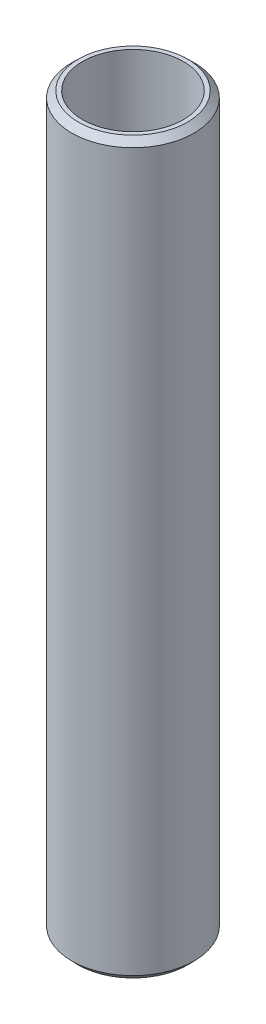
SolidWorks part; units mm, degrees
ref_plane "Front Plane" through (0, 0, 0) normal (0, 0, 1) x (1, 0, 0)
ref_plane "Top Plane" through (0, 0, 0) normal (0, 1, 0) x (1, 0, 0)
ref_plane "Right Plane" through (0, 0, 0) normal (1, 0, 0) x (0, 0, -1)
sketch "Sketch1" plane through (0, 0, 0) normal (0, 1, 0) x (1, 0, 0)
  circle A0 centre (0, 0) radius 30
  dimension "SHAFT_OD" = 60
extrude "Boss-Extrude1" add sketch "Sketch1" along normal blind 358.1775
sketch "Sketch2" plane through (0, 0, 0) normal (0, 1, 0) x (1, 0, 0)
  circle A0 centre (0, 0) radius 24.7586
  dimension "BORE_D" = 49.5171
extrude "Cut-Extrude1" cut sketch "Sketch2" along normal through all
chamfer "Chamfer1" distance 3.0856 angle 45.964 2 edges at (0, 358.1775, 30) (0, 0, 30) first distance on face at (0, 358.1775, 30) first distance on face at (0, 0, 24.7586)
